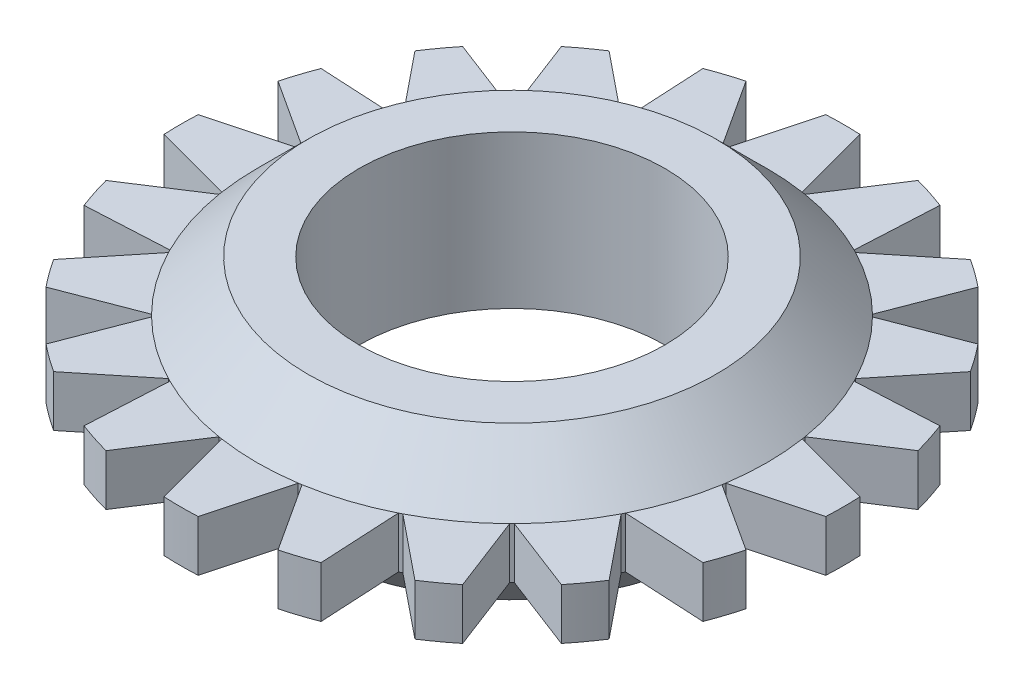
SolidWorks part; units mm, degrees
ref_plane "前视基准面" through (0, 0, 0) normal (0, 0, 1) x (1, 0, 0)
ref_plane "上视基准面" through (0, 0, 0) normal (0, 1, 0) x (1, 0, 0)
ref_plane "右视基准面" through (0, 0, 0) normal (1, 0, 0) x (0, 0, -1)
other "Configuration Table"
sketch "草图2" plane through (0, 0, 0) normal (0, 1, 0) x (1, 0, 0)
  circle A0 centre (0, 0) radius 50
  circle A1 centre (0, 0) radius 30
  dimension "D1" = 100
  dimension "D2" = 60
sketch "草图1" plane through (0, 0, 0) normal (0, 1, 0) x (1, 0, 0)
  line L0 (0, 0) -> (0, 103.3216) construction
  line L1 (-3.3524, 64.9135) -> (-7.5, 49.4343)
  line L2 (3.3524, 64.9135) -> (7.5, 49.4343)
  line L3 (16.8711, 62.7723) -> (8.1431, 49.3324)
  line L4 (23.2477, 60.7005) -> (22.409, 44.6972)
  line L5 (35.4431, 54.4866) -> (22.9891, 44.4016)
  line L6 (40.8673, 50.5457) -> (35.1244, 35.5848)
  line L7 (50.5457, 40.8673) -> (35.5848, 35.1244)
  line L8 (54.4866, 35.4431) -> (44.4016, 22.9891)
  line L9 (60.7005, 23.2477) -> (44.6972, 22.409)
  line L10 (62.7723, 16.8711) -> (49.3324, 8.1431)
  line L11 (64.9135, 3.3524) -> (49.4343, 7.5)
  line L12 (64.9135, -3.3524) -> (49.4343, -7.5)
  line L13 (62.7723, -16.8711) -> (49.3324, -8.1431)
  line L14 (60.7005, -23.2477) -> (44.6972, -22.409)
  line L15 (54.4866, -35.4431) -> (44.4016, -22.9891)
  line L16 (50.5457, -40.8673) -> (35.5848, -35.1244)
  line L17 (40.8673, -50.5457) -> (35.1244, -35.5848)
  line L18 (35.4431, -54.4866) -> (22.9891, -44.4016)
  line L19 (23.2477, -60.7005) -> (22.409, -44.6972)
  line L20 (16.8711, -62.7723) -> (8.1431, -49.3324)
  line L21 (3.3524, -64.9135) -> (7.5, -49.4343)
  line L22 (-3.3524, -64.9135) -> (-7.5, -49.4343)
  line L23 (-16.8711, -62.7723) -> (-8.1431, -49.3324)
  line L24 (-23.2477, -60.7005) -> (-22.409, -44.6972)
  line L25 (-35.4431, -54.4866) -> (-22.9891, -44.4016)
  line L26 (-40.8673, -50.5457) -> (-35.1244, -35.5848)
  line L27 (-50.5457, -40.8673) -> (-35.5848, -35.1244)
  line L28 (-54.4866, -35.4431) -> (-44.4016, -22.9891)
  line L29 (-60.7005, -23.2477) -> (-44.6972, -22.409)
  line L30 (-62.7723, -16.8711) -> (-49.3324, -8.1431)
  line L31 (-64.9135, -3.3524) -> (-49.4343, -7.5)
  line L32 (-64.9135, 3.3524) -> (-49.4343, 7.5)
  line L33 (-62.7723, 16.8711) -> (-49.3324, 8.1431)
  line L34 (-60.7005, 23.2477) -> (-44.6972, 22.409)
  line L35 (-54.4866, 35.4431) -> (-44.4016, 22.9891)
  line L36 (-50.5457, 40.8673) -> (-35.5848, 35.1244)
  line L37 (-40.8673, 50.5457) -> (-35.1244, 35.5848)
  line L38 (-35.4431, 54.4866) -> (-22.9891, 44.4016)
  line L39 (-23.2477, 60.7005) -> (-22.409, 44.6972)
  line L40 (-16.8711, 62.7723) -> (-8.1431, 49.3324)
  arc A0 (7.5, 49.4343) -> (-7.5, 49.4343) centre (0, 0) ccw
  arc A1 (3.3524, 64.9135) -> (-3.3524, 64.9135) centre (0, 0) ccw
  arc A2 (22.409, 44.6972) -> (8.1431, 49.3324) centre (0, 0) ccw
  arc A3 (23.2477, 60.7005) -> (16.8711, 62.7723) centre (0, 0) ccw
  arc A4 (35.1244, 35.5848) -> (22.9891, 44.4016) centre (0, 0) ccw
  arc A5 (40.8673, 50.5457) -> (35.4431, 54.4866) centre (0, 0) ccw
  arc A6 (44.4016, 22.9891) -> (35.5848, 35.1244) centre (0, 0) ccw
  arc A7 (54.4866, 35.4431) -> (50.5457, 40.8673) centre (0, 0) ccw
  arc A8 (49.3324, 8.1431) -> (44.6972, 22.409) centre (0, 0) ccw
  arc A9 (62.7723, 16.8711) -> (60.7005, 23.2477) centre (0, 0) ccw
  arc A10 (49.4343, -7.5) -> (49.4343, 7.5) centre (0, 0) ccw
  arc A11 (64.9135, -3.3524) -> (64.9135, 3.3524) centre (0, 0) ccw
  arc A12 (44.6972, -22.409) -> (49.3324, -8.1431) centre (0, 0) ccw
  arc A13 (60.7005, -23.2477) -> (62.7723, -16.8711) centre (0, 0) ccw
  arc A14 (35.5848, -35.1244) -> (44.4016, -22.9891) centre (0, 0) ccw
  arc A15 (50.5457, -40.8673) -> (54.4866, -35.4431) centre (0, 0) ccw
  arc A16 (22.9891, -44.4016) -> (35.1244, -35.5848) centre (0, 0) ccw
  arc A17 (35.4431, -54.4866) -> (40.8673, -50.5457) centre (0, 0) ccw
  arc A18 (8.1431, -49.3324) -> (22.409, -44.6972) centre (0, 0) ccw
  arc A19 (16.8711, -62.7723) -> (23.2477, -60.7005) centre (0, 0) ccw
  arc A20 (-7.5, -49.4343) -> (7.5, -49.4343) centre (0, 0) ccw
  arc A21 (-3.3524, -64.9135) -> (3.3524, -64.9135) centre (0, 0) ccw
  arc A22 (-22.409, -44.6972) -> (-8.1431, -49.3324) centre (0, 0) ccw
  arc A23 (-23.2477, -60.7005) -> (-16.8711, -62.7723) centre (0, 0) ccw
  arc A24 (-35.1244, -35.5848) -> (-22.9891, -44.4016) centre (0, 0) ccw
  arc A25 (-40.8673, -50.5457) -> (-35.4431, -54.4866) centre (0, 0) ccw
  arc A26 (-44.4016, -22.9891) -> (-35.5848, -35.1244) centre (0, 0) ccw
  arc A27 (-54.4866, -35.4431) -> (-50.5457, -40.8673) centre (0, 0) ccw
  arc A28 (-49.3324, -8.1431) -> (-44.6972, -22.409) centre (0, 0) ccw
  arc A29 (-62.7723, -16.8711) -> (-60.7005, -23.2477) centre (0, 0) ccw
  arc A30 (-49.4343, 7.5) -> (-49.4343, -7.5) centre (0, 0) ccw
  arc A31 (-64.9135, 3.3524) -> (-64.9135, -3.3524) centre (0, 0) ccw
  arc A32 (-44.6972, 22.409) -> (-49.3324, 8.1431) centre (0, 0) ccw
  arc A33 (-60.7005, 23.2477) -> (-62.7723, 16.8711) centre (0, 0) ccw
  arc A34 (-35.5848, 35.1244) -> (-44.4016, 22.9891) centre (0, 0) ccw
  arc A35 (-50.5457, 40.8673) -> (-54.4866, 35.4431) centre (0, 0) ccw
  arc A36 (-22.9891, 44.4016) -> (-35.1244, 35.5848) centre (0, 0) ccw
  arc A37 (-35.4431, 54.4866) -> (-40.8673, 50.5457) centre (0, 0) ccw
  arc A38 (-8.1431, 49.3324) -> (-22.409, 44.6972) centre (0, 0) ccw
  arc A39 (-16.8711, 62.7723) -> (-23.2477, 60.7005) centre (0, 0) ccw
  point P86 (0, 0)
  dimension "D1" = 100
  dimension "D2" = 130
  dimension "D3" = 30
  dimension "D4" = 15
  dimension "D5" = 20
extrude "凸台-拉伸1" add sketch "草图1" along normal mid plane 10
extrude "凸台-拉伸2" add sketch "草图2" along normal mid plane 30
chamfer "倒角1" distance 10 angle 45 2 edges at (0, -15, 50) (0, 15, 50)
